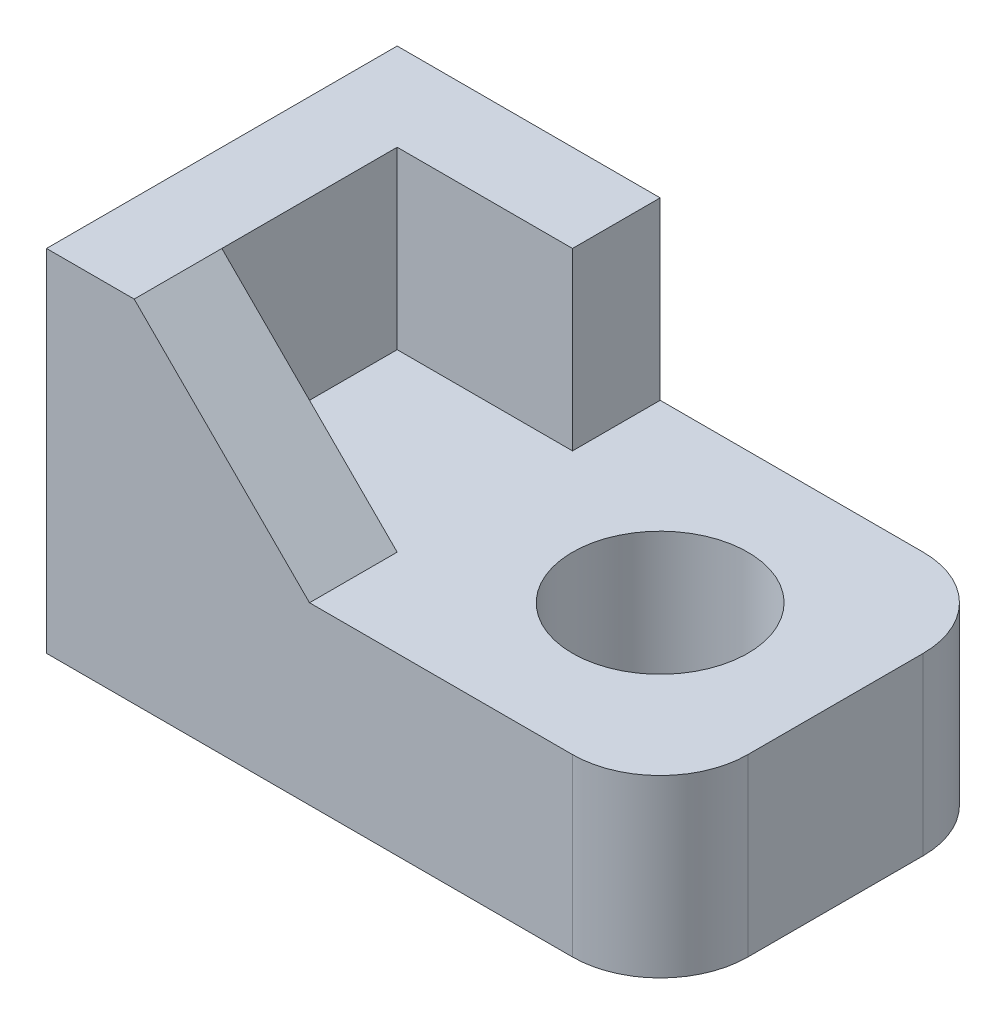
SolidWorks part; units mm, degrees
ref_plane "Front Plane" through (0, 0, 0) normal (0, 0, 1) x (1, 0, 0)
ref_plane "Top Plane" through (0, 0, 0) normal (0, 1, 0) x (1, 0, 0)
ref_plane "Right Plane" through (0, 0, 0) normal (1, 0, 0) x (0, 0, -1)
sketch "Sketch2" plane through (0, 0, 0) normal (0, 1, 0) x (1, 0, 0)
  line L0 (30, 40) -> (30, 30)
  line L1 (60, 40) -> (0, 40)
  line L2 (70, 30) -> (70, 10)
  line L3 (60, 0) -> (0, 0)
  line L4 (0, 40) -> (0, 0)
  line L5 (30, 30) -> (10, 30)
  line L6 (10, 30) -> (10, 10)
  line L7 (10, 10) -> (30, 10)
  line L8 (30, 10) -> (30, 0)
  circle A0 centre (50, 20) radius 10
  arc A1 (60, 0) -> (70, 10) centre (60, 10) ccw
  arc A2 (60, 40) -> (70, 30) centre (60, 30) cw
  point P15 (70, 0)
  dimension "D5" = 30
  dimension "D3" = 20
  dimension "D10" = 10
  dimension "D1" = 70
  dimension "D2" = 40
  dimension "D4" = 50
  dimension "D6" = 10
  dimension "D7" = 10
  dimension "D8" = 10
  dimension "D9" = 30
extrude "Boss-Extrude1" add sketch "Sketch2" along normal blind 20 contours A2 L1 L0 L5 L6 L7 L8 L3 A1 L2 A0 region at (45, 0, -39.2789)
extrude "Boss-Extrude2" add sketch "Sketch2<9>" along normal blind 40 contours L8 L7 L6 L5 L0 L1 L4 L3 region at (29.5, 0, -35)
sketch "Sketch2<9>" plane through (0, 0, 0) normal (0, 1, 0) x (1, 0, 0) same geometry as "Sketch2"
fillet "Chamfer1" radius 20 1 edges at (30, 40, -5) profile chamfer
